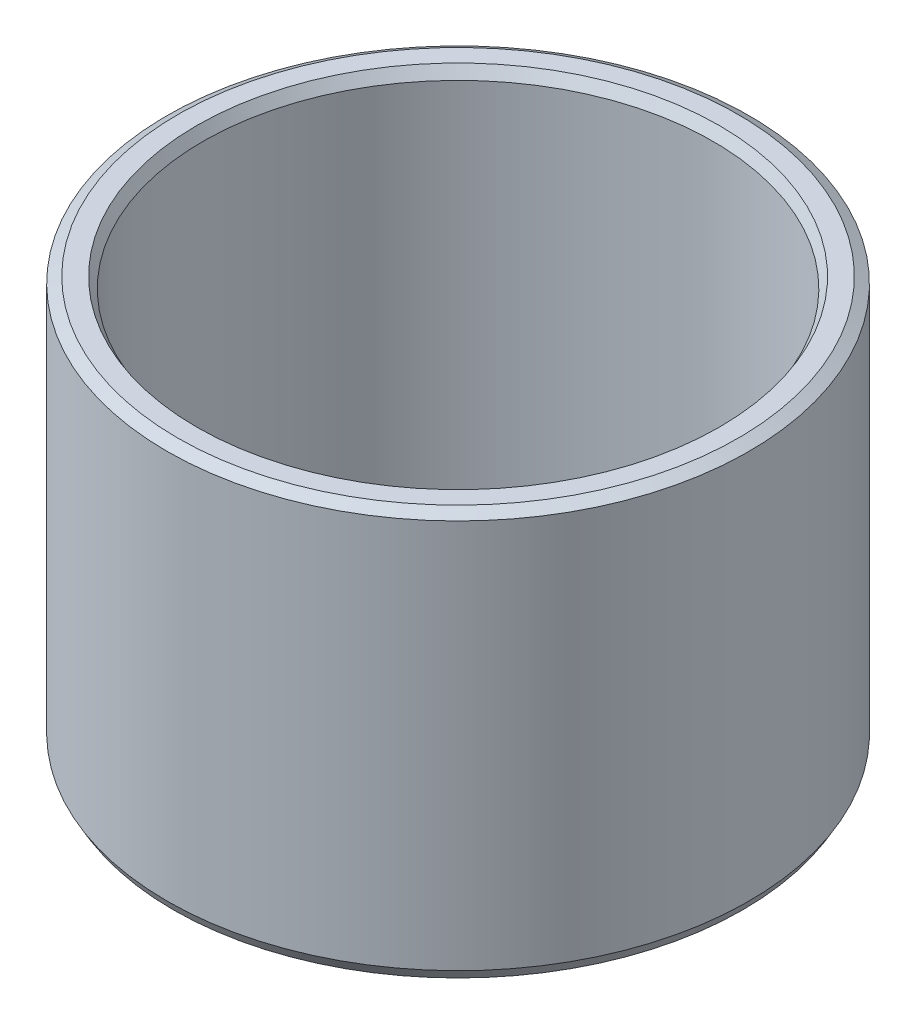
SolidWorks part; units mm, degrees
ref_plane "Front Plane" through (0, 0, 0) normal (0, 0, 1) x (1, 0, 0)
ref_plane "Top Plane" through (0, 0, 0) normal (0, 1, 0) x (1, 0, 0)
ref_plane "Right Plane" through (0, 0, 0) normal (1, 0, 0) x (0, 0, -1)
sketch "Sketch1" plane through (0, 0, 0) normal (0, 1, 0) x (1, 0, 0)
  circle A0 centre (0, 0) radius 52.5
  dimension "SLEEVE_OD" = 105
extrude "Boss-Extrude1" add sketch "Sketch1" along normal blind 73.3216
sketch "Sketch2" plane through (0, 0, 0) normal (0, 1, 0) x (1, 0, 0)
  circle A0 centre (0, 0) radius 46.0392
  dimension "BORE_D" = 92.0785
extrude "Cut-Extrude1" cut sketch "Sketch2" along normal through all
chamfer "Chamfer1" distance 1.1124 angle 60 4 edges at (0, 73.3216, 46.0392) (0, 0, 46.0392) (0, 0, 52.5) (0, 73.3216, 52.5) first distance on face at (0, 73.3216, 46.0392) first distance on face at (0, 0, 46.0392) first distance on face at (0, 73.3216, 52.5)
